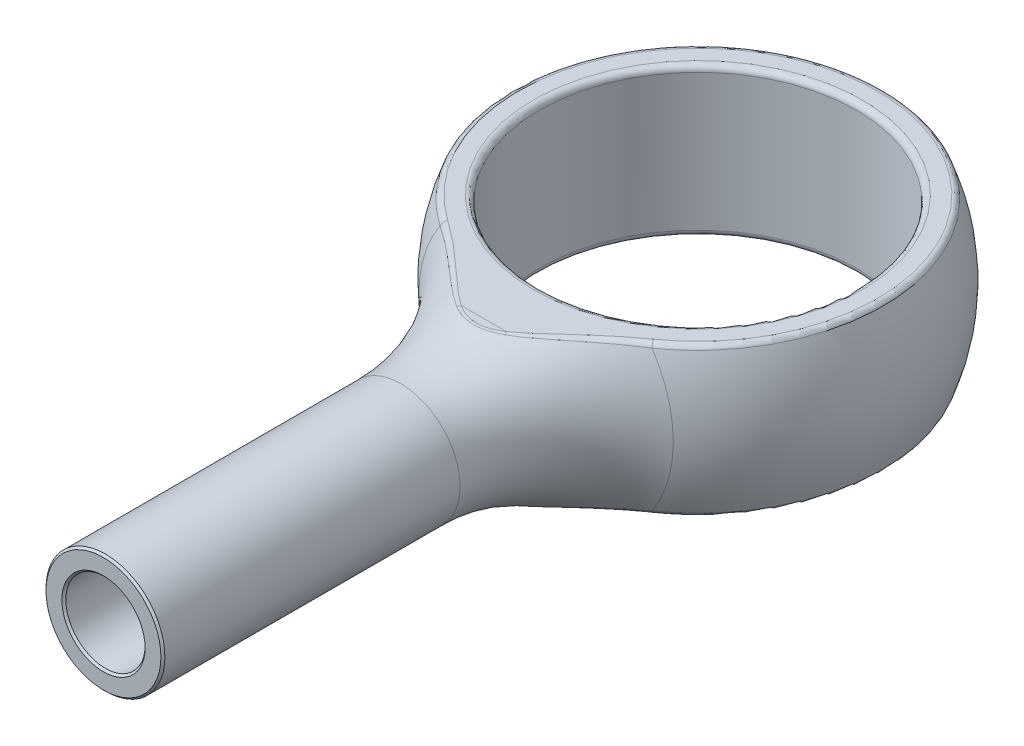
SolidWorks part; units mm, degrees
ref_plane "Front Plane" through (0, 0, 0) normal (0, 0, 1) x (1, 0, 0)
ref_plane "Top Plane" through (0, 0, 0) normal (0, 1, 0) x (1, 0, 0)
ref_plane "Right Plane" through (0, 0, 0) normal (1, 0, 0) x (0, 0, -1)
sketch "Sketch1" plane through (0, 0, 0) normal (0, 1, 0) x (1, 0, 0)
  line L0 (-1.5, -15) -> (1.5, -15)
  line L1 (1.5, -15) -> (1.5, -7.5)
  line L2 (-1.5, -15) -> (-1.5, -7.5)
  circle A0 centre (0, 0) radius 5
  circle A1 centre (0, 0) radius 4
  circle A2 centre (0, 0) radius 2 construction
  arc A3 (-1.5, -7.5) -> (-3.2117, -3.8321) centre (-6.2857, -7.5) ccw
  arc A4 (1.5, -7.5) -> (3.2117, -3.8321) centre (6.2857, -7.5) cw
  point P7 (0, -15)
  point P14 (0, 0)
  dimension "D1" = 10
  dimension "D2" = 8
  dimension "D3" = 4
  dimension "D4" = 15
  dimension "D5" = 3
  dimension "D6" = 7.5
sketch "Sketch2" plane through (0, 0, 0) normal (0, 1, 0) x (1, 0, 0)
  line L0 (-1.5, -15) -> (1.5, -15) construction
  line L1 (-1.5, -15) -> (-1.5, -7.5) construction
  line L2 (-1.5, -15) -> (0, -15)
  line L3 (-1.5, -15) -> (-1.5, -7.5)
  line L4 (0, 5) -> (0, -15)
  arc A0 (-1.5, -7.5) -> (-3.2117, -3.8321) centre (-6.2857, -7.5) ccw construction
  circle A1 centre (0, 0) radius 5 construction
  arc A2 (-1.5, -7.5) -> (-3.2117, -3.8321) centre (-6.2857, -7.5) ccw
  arc A3 (0, 5) -> (-3.2117, -3.8321) centre (0, 0) ccw
revolve "Revolve1" add sketch "Sketch2" angle 360 about L4
sketch "Sketch3" plane through (0, 0, 0) normal (1, 0, 0) x (0, 0, -1)
  line L0 (-16.8319, 8.7723) -> (6.7007, 8.7723)
  line L1 (6.7007, 8.7723) -> (6.7007, 1.875)
  line L2 (6.7007, 1.875) -> (-5.4051, 1.875)
  line L3 (-8.273, 2.7792) -> (-16.8319, 8.7723)
  line L4 (0, 0) -> (11.3583, 0) construction
  line L5 (-8.273, -2.7792) -> (-16.8319, -8.7723)
  line L6 (6.7007, -1.875) -> (-5.4051, -1.875)
  line L7 (6.7007, -8.7723) -> (6.7007, -1.875)
  line L8 (-16.8319, -8.7723) -> (6.7007, -8.7723)
  arc A0 (-5.4051, 1.875) -> (-8.273, 2.7792) centre (-5.4051, 6.875) cw
  arc A1 (-5.4051, -1.875) -> (-8.273, -2.7792) centre (-5.4051, -6.875) ccw
  point P15 (0, 0)
  point P16 (-16.8319, 8.7723)
  dimension "D1" = 5
  dimension "D2" = 145
  dimension "D3" = 3.75
extrude "Cut-Extrude1" cut sketch "Sketch3" against normal blind 10 and the other way blind 10
sketch "Sketch4" plane through (0, 0, 0) normal (0, 1, 0) x (1, 0, 0)
  circle A0 centre (0, 0) radius 4 construction
  circle A1 centre (0, 0) radius 4
extrude "Cut-Extrude2" cut sketch "Sketch4" against normal blind 10 and the other way blind 10
fillet "Fillet1" radius 0.15 10 edges at (0, 1.875, 4) (0, -1.875, -4) (0, -1.875, -4.6351) (0.013, -1.8801, 5.6308) (0, 1.875, -4.6351) (-0.013, 1.8801, 5.6308)
sketch "Sketch5" plane through (0, 0, 15) normal (0, 0, 1) x (1, 0, 0)
  circle A0 centre (0, 0) radius 1
  dimension "D1" = 2
extrude "Cut-Extrude3" cut sketch "Sketch5" against normal blind 5
chamfer "Chamfer1" distance 0.05 angle 45 2 edges at (-1.5, 0, 15) (1, 0, 15)
